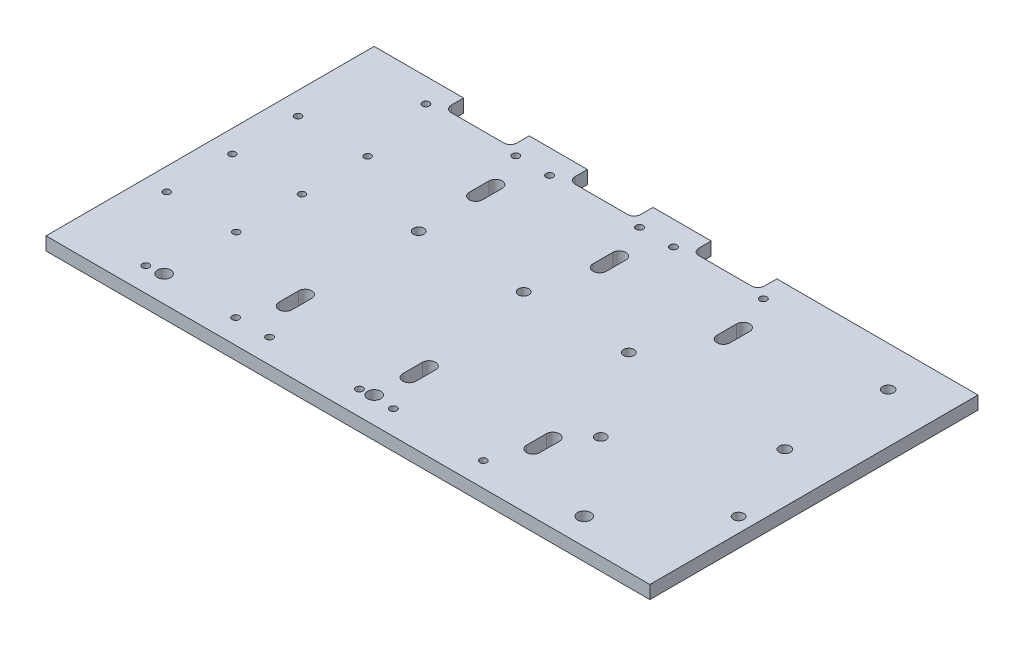
SolidWorks part; units mm, degrees
ref_plane "Front Plane" through (0, 0, 0) normal (0, 0, 1) x (1, 0, 0)
ref_plane "Top Plane" through (0, 0, 0) normal (0, 1, 0) x (1, 0, 0)
ref_plane "Right Plane" through (0, 0, 0) normal (1, 0, 0) x (0, 0, -1)
sketch "Sketch1" plane through (0, 0, 0) normal (0, 1, 0) x (1, 0, 0)
  line L1 (0, 0) -> (292.1, 0)
  line L2 (0, 0) -> (0, 158.75)
  line L3 (0, 158.75) -> (292.1, 158.75)
  line L4 (292.1, 0) -> (292.1, 158.75)
  dimension "D1" = 292.1
  dimension "D2" = 158.75
extrude "Boss-Extrude1" add sketch "Sketch1" along normal blind 6.35
sketch "Sketch2" plane through (0, 6.35, 0) normal (0, 1, 0) x (1, 0, 0)
  line L0 (0, 25.4) -> (292.1, 25.4) construction
  line L1 (0, 12.7) -> (292.1, 12.7) construction
  line L3 (146.05, 25.4) -> (146.05, 158.75) construction
  line L4 (0, 158.75) -> (0, 0)
  line L5 (0, 0) -> (292.1, 0)
  line L6 (292.1, 0) -> (292.1, 158.75)
  line L7 (292.1, 158.75) -> (0, 158.75)
  line L8 (0, 158.75) -> (0, 0) construction
  line L9 (0, 0) -> (292.1, 0) construction
  line L10 (292.1, 0) -> (292.1, 158.75) construction
  line L11 (292.1, 158.75) -> (0, 158.75) construction
  line L12 (292.1, 92.075) -> (0, 92.075) construction
  circle A0 centre (146.05, 12.7) radius 3.175
  circle A1 centre (247.65, 12.7) radius 3.175
  circle A2 centre (44.45, 12.7) radius 3.175
  point P8 (146.05, 92.075)
  dimension "D6" = 6.35
  dimension "D7" = 6.35
  dimension "D8" = 6.35
  dimension "D2" = 25.4
  dimension "D3" = 12.7
  dimension "D4" = 101.6
  dimension "D5" = 101.6
  dimension "D1" = 0
extrude "Cut-Extrude2" cut sketch "Sketch2" against normal blind 6.35
ref_plane "Plane2" through (0, 0, -79.375) normal (0, 0, 1) x (1, 0, 0)
ref_plane "Plane3" through (146.05, 0, 0) normal (-1, 0, 0) x (0, 0, 1)
ref_plane "Plane4" through (0, 0, -92.075) normal (0, 0, -1) x (-1, 0, 0)
sketch "Sketch4" plane through (0, 6.35, 0) normal (0, 1, 0) x (1, 0, 0)
  line L0 (92.964, 94.615) -> (83.439, 94.615) construction
  line L1 (83.439, 89.535) -> (92.964, 89.535) construction
  line L2 (143.764, 94.615) -> (134.239, 94.615) construction
  line L3 (134.239, 89.535) -> (143.764, 89.535) construction
  line L4 (194.564, 94.615) -> (185.039, 94.615) construction
  line L5 (185.039, 89.535) -> (194.564, 89.535) construction
  line L6 (270.764, 94.133) -> (270.764, 84.467) construction
  line L7 (265.43, 84.467) -> (265.43, 94.133) construction
  line L8 (265.43, 134.467) -> (265.43, 144.133) construction
  line L9 (270.764, 144.133) -> (270.764, 134.467) construction
  line L10 (211.4042, 52.4764) -> (218.4146, 52.4764)
  line L11 (211.4042, 74.4728) -> (211.4042, 52.4764)
  line L12 (292.1, 74.4728) -> (211.4042, 74.4728)
  line L13 (292.1, 52.4764) -> (292.1, 74.4728)
  line L14 (285.0896, 52.4764) -> (292.1, 52.4764)
  line L15 (292.1, 47.3964) -> (285.0896, 47.3964)
  line L16 (292.1, 25.4) -> (292.1, 47.3964)
  line L17 (211.4042, 25.4) -> (292.1, 25.4)
  line L18 (211.4042, 47.3964) -> (211.4042, 25.4)
  line L19 (218.4146, 47.3964) -> (211.4042, 47.3964)
  line L20 (211.4042, 52.4764) -> (218.4146, 52.4764) construction
  line L21 (211.4042, 74.4728) -> (211.4042, 52.4764) construction
  line L22 (292.1, 74.4728) -> (211.4042, 74.4728) construction
  line L23 (292.1, 52.4764) -> (292.1, 74.4728) construction
  line L24 (285.0896, 52.4764) -> (292.1, 52.4764) construction
  line L25 (292.1, 47.3964) -> (285.0896, 47.3964) construction
  line L26 (292.1, 25.4) -> (292.1, 47.3964) construction
  line L27 (211.4042, 25.4) -> (292.1, 25.4) construction
  line L28 (211.4042, 47.3964) -> (211.4042, 25.4) construction
  line L29 (218.4146, 47.3964) -> (211.4042, 47.3964) construction
  line L30 (92.964, 94.615) -> (83.439, 94.615) construction
  line L31 (83.439, 89.535) -> (92.964, 89.535) construction
  line L32 (143.764, 94.615) -> (134.239, 94.615) construction
  line L33 (134.239, 89.535) -> (143.764, 89.535) construction
  line L34 (194.564, 94.615) -> (185.039, 94.615) construction
  line L35 (185.039, 89.535) -> (194.564, 89.535) construction
  line L36 (270.764, 94.133) -> (270.764, 84.467) construction
  line L37 (265.43, 84.467) -> (265.43, 94.133) construction
  line L38 (265.43, 134.467) -> (265.43, 144.133) construction
  line L39 (270.764, 144.133) -> (270.764, 134.467) construction
  line L40 (194.564, 92.075) -> (185.039, 92.075) construction
  line L41 (185.039, 92.075) -> (143.764, 92.075) construction
  line L42 (143.764, 92.075) -> (134.239, 92.075) construction
  line L43 (134.239, 92.075) -> (92.964, 92.075) construction
  line L44 (92.964, 92.075) -> (83.439, 92.075) construction
  line L45 (268.097, 84.467) -> (268.097, 94.133) construction
  line L46 (268.097, 94.133) -> (268.097, 134.467) construction
  line L47 (268.097, 134.467) -> (268.097, 144.133) construction
  line L48 (153.9042, 9.125) -> (153.9042, 149.625) construction
  line L49 (153.9042, 149.625) -> (203.9042, 149.625) construction
  line L50 (203.9042, 149.625) -> (203.9042, 9.125) construction
  line L51 (203.9042, 9.125) -> (153.9042, 9.125) construction
  line L52 (34.1164, 149.625) -> (34.1164, 9.125)
  line L53 (84.1164, 149.625) -> (34.1164, 149.625)
  line L54 (84.1164, 9.125) -> (84.1164, 149.625)
  line L55 (34.1164, 9.125) -> (84.1164, 9.125)
  line L56 (34.1164, 149.625) -> (34.1164, 9.125) construction
  line L57 (84.1164, 149.625) -> (34.1164, 149.625) construction
  line L58 (84.1164, 9.125) -> (84.1164, 149.625) construction
  line L59 (34.1164, 9.125) -> (84.1164, 9.125) construction
  line L60 (94.0103, 9.125) -> (94.0103, 149.625) construction
  line L61 (94.0103, 149.625) -> (144.0103, 149.625) construction
  line L62 (144.0103, 149.625) -> (144.0103, 9.125) construction
  line L63 (144.0103, 9.125) -> (94.0103, 9.125) construction
  line L64 (153.9042, 9.125) -> (153.9042, 149.625) construction
  line L65 (153.9042, 149.625) -> (203.9042, 149.625) construction
  line L66 (203.9042, 149.625) -> (203.9042, 9.125) construction
  line L67 (203.9042, 9.125) -> (153.9042, 9.125) construction
  line L68 (94.0103, 9.125) -> (94.0103, 149.625) construction
  line L69 (94.0103, 149.625) -> (144.0103, 149.625) construction
  line L70 (144.0103, 149.625) -> (144.0103, 9.125) construction
  line L71 (144.0103, 9.125) -> (94.0103, 9.125) construction
  line L72 (147.1853, 130.175) -> (147.1853, 120.65) construction
  line L73 (150.3603, 130.175) -> (150.3603, 120.65)
  line L74 (144.0103, 130.175) -> (144.0103, 120.65)
  line L75 (207.0792, 130.175) -> (207.0792, 120.65) construction
  line L76 (210.2542, 130.175) -> (210.2542, 120.65)
  line L77 (203.9042, 130.175) -> (203.9042, 120.65)
  line L78 (87.2914, 130.175) -> (87.2914, 120.65) construction
  line L79 (90.4664, 130.175) -> (90.4664, 120.65)
  line L80 (84.1164, 130.175) -> (84.1164, 120.65)
  line L81 (147.1853, 130.175) -> (87.2914, 130.175) construction
  line L82 (87.2914, 38.1) -> (87.2914, 28.575) construction
  line L83 (90.4664, 38.1) -> (90.4664, 28.575)
  line L84 (84.1164, 38.1) -> (84.1164, 28.575)
  line L85 (207.0792, 38.1) -> (207.0792, 28.575) construction
  line L86 (210.2542, 38.1) -> (210.2542, 28.575)
  line L87 (203.9042, 38.1) -> (203.9042, 28.575)
  line L88 (147.1853, 38.1) -> (147.1853, 28.575) construction
  line L89 (150.3603, 38.1) -> (150.3603, 28.575)
  line L90 (144.0103, 38.1) -> (144.0103, 28.575)
  line L91 (147.1853, 28.575) -> (207.0792, 28.575) construction
  line L92 (207.0792, 28.575) -> (63.9767, 28.575) construction
  line L93 (147.1853, 120.65) -> (147.1853, 38.1) construction
  line L94 (207.0792, 120.65) -> (207.0792, 38.1) construction
  line L95 (87.2914, 120.65) -> (87.2914, 74.3204) construction
  line L96 (292.1, 25.4) -> (0, 25.4) construction
  line L97 (292.1, 25.4) -> (0, 25.4) construction
  line L98 (191.6042, 152.8) -> (166.2042, 152.8) construction
  line L99 (191.6042, 149.625) -> (166.2042, 149.625)
  line L100 (76.2, 117.475) -> (215.9, 117.475) construction
  line L101 (131.7103, 152.8) -> (106.3103, 152.8) construction
  line L102 (131.7103, 149.625) -> (106.3103, 149.625)
  line L103 (76.2, 117.475) -> (215.9, 117.475) construction
  line L104 (71.8164, 152.8) -> (46.4164, 152.8) construction
  line L105 (71.8164, 149.625) -> (46.4164, 149.625)
  line L107 (178.9042, 9.125) -> (178.9042, 158.75) construction
  line L108 (119.0103, 9.125) -> (119.0103, 158.75) construction
  line L109 (59.1164, 9.125) -> (59.1164, 158.75) construction
  line L110 (166.2042, 152.8) -> (131.7103, 152.8) construction
  line L111 (106.3103, 152.8) -> (71.8164, 152.8) construction
  line L112 (163.0292, 152.8) -> (163.0292, 158.75)
  line L113 (194.7792, 152.8) -> (194.7792, 158.75)
  line L114 (134.8853, 152.8) -> (134.8853, 158.75)
  line L115 (103.1353, 152.8) -> (103.1353, 158.75)
  line L116 (147.1853, 74.3204) -> (207.0792, 74.3204) construction
  line L117 (207.0792, 74.3204) -> (87.2914, 74.3204) construction
  line L118 (0, 133.35) -> (292.1, 133.35) construction
  line L119 (0, 158.75) -> (0, 0) construction
  line L120 (292.1, 0) -> (292.1, 158.75) construction
  line L121 (292.1, 158.75) -> (0, 158.75) construction
  line L122 (43.2414, 152.8) -> (43.2414, 158.75)
  line L123 (74.9914, 152.8) -> (74.9914, 158.75)
  line L124 (74.9914, 158.75) -> (43.2414, 158.75)
  line L125 (134.8853, 158.75) -> (103.1353, 158.75)
  line L126 (194.7792, 158.75) -> (163.0292, 158.75)
  line L144 (87.2914, 74.3204) -> (87.2914, 9.0265) construction
  circle A0 centre (88.2015, 92.075) radius 2.54
  arc A1 (92.964, 89.535) -> (92.964, 94.615) centre (92.964, 92.075) ccw construction
  arc A2 (83.439, 94.615) -> (83.439, 89.535) centre (83.439, 92.075) ccw construction
  arc A3 (285.0896, 52.4764) -> (285.0896, 47.3964) centre (285.0896, 49.9364) ccw
  arc A4 (218.4146, 47.3964) -> (218.4146, 52.4764) centre (218.4146, 49.9364) ccw
  arc A5 (285.0896, 52.4764) -> (285.0896, 47.3964) centre (285.0896, 49.9364) ccw construction
  arc A6 (218.4146, 47.3964) -> (218.4146, 52.4764) centre (218.4146, 49.9364) ccw construction
  arc A7 (134.239, 94.615) -> (134.239, 89.535) centre (134.239, 92.075) ccw construction
  arc A8 (143.764, 89.535) -> (143.764, 94.615) centre (143.764, 92.075) ccw construction
  arc A9 (185.039, 94.615) -> (185.039, 89.535) centre (185.039, 92.075) ccw construction
  arc A10 (194.564, 89.535) -> (194.564, 94.615) centre (194.564, 92.075) ccw construction
  arc A11 (265.43, 84.467) -> (270.764, 84.467) centre (268.097, 84.467) ccw construction
  arc A12 (270.764, 94.133) -> (265.43, 94.133) centre (268.097, 94.133) ccw construction
  arc A13 (265.43, 134.467) -> (270.764, 134.467) centre (268.097, 134.467) ccw construction
  arc A14 (270.764, 144.133) -> (265.43, 144.133) centre (268.097, 144.133) ccw construction
  arc A15 (92.964, 89.535) -> (92.964, 94.615) centre (92.964, 92.075) ccw construction
  arc A16 (83.439, 94.615) -> (83.439, 89.535) centre (83.439, 92.075) ccw construction
  arc A17 (134.239, 94.615) -> (134.239, 89.535) centre (134.239, 92.075) ccw construction
  arc A18 (143.764, 89.535) -> (143.764, 94.615) centre (143.764, 92.075) ccw construction
  arc A19 (185.039, 94.615) -> (185.039, 89.535) centre (185.039, 92.075) ccw construction
  arc A20 (194.564, 89.535) -> (194.564, 94.615) centre (194.564, 92.075) ccw construction
  arc A21 (265.43, 84.467) -> (270.764, 84.467) centre (268.097, 84.467) ccw construction
  arc A22 (270.764, 94.133) -> (265.43, 94.133) centre (268.097, 94.133) ccw construction
  arc A23 (265.43, 134.467) -> (270.764, 134.467) centre (268.097, 134.467) ccw construction
  arc A24 (270.764, 144.133) -> (265.43, 144.133) centre (268.097, 144.133) ccw construction
  circle A25 centre (44.45, 111.125) radius 1.651 construction
  circle A26 centre (44.45, 79.375) radius 1.651 construction
  circle A27 centre (44.45, 47.625) radius 1.651 construction
  circle A28 centre (10.795, 111.125) radius 1.651 construction
  circle A29 centre (10.795, 79.375) radius 1.651 construction
  circle A30 centre (10.795, 47.625) radius 1.651 construction
  circle A31 centre (44.45, 111.125) radius 1.651
  circle A32 centre (44.45, 79.375) radius 1.651
  circle A33 centre (44.45, 47.625) radius 1.651
  circle A34 centre (10.795, 111.125) radius 1.651
  circle A35 centre (10.795, 79.375) radius 1.651
  circle A36 centre (10.795, 47.625) radius 1.651
  circle A37 centre (139.0015, 92.075) radius 2.54
  circle A38 centre (189.8015, 92.075) radius 2.54
  circle A39 centre (218.4146, 49.9364) radius 2.54
  circle A40 centre (285.0896, 49.9364) radius 2.54
  circle A41 centre (268.097, 139.3) radius 2.667
  circle A42 centre (268.097, 89.3) radius 2.667
  arc A43 (150.3603, 130.175) -> (144.0103, 130.175) centre (147.1853, 130.175) ccw
  arc A44 (144.0103, 120.65) -> (150.3603, 120.65) centre (147.1853, 120.65) ccw
  arc A45 (210.2542, 130.175) -> (203.9042, 130.175) centre (207.0792, 130.175) ccw
  arc A46 (203.9042, 120.65) -> (210.2542, 120.65) centre (207.0792, 120.65) ccw
  arc A47 (90.4664, 130.175) -> (84.1164, 130.175) centre (87.2914, 130.175) ccw
  arc A48 (84.1164, 120.65) -> (90.4664, 120.65) centre (87.2914, 120.65) ccw
  arc A49 (90.4664, 38.1) -> (84.1164, 38.1) centre (87.2914, 38.1) ccw
  arc A50 (84.1164, 28.575) -> (90.4664, 28.575) centre (87.2914, 28.575) ccw
  arc A51 (210.2542, 38.1) -> (203.9042, 38.1) centre (207.0792, 38.1) ccw
  arc A52 (203.9042, 28.575) -> (210.2542, 28.575) centre (207.0792, 28.575) ccw
  arc A53 (150.3603, 38.1) -> (144.0103, 38.1) centre (147.1853, 38.1) ccw
  arc A54 (144.0103, 28.575) -> (150.3603, 28.575) centre (147.1853, 28.575) ccw
  arc A55 (191.6042, 149.625) -> (194.7792, 152.8) centre (191.6042, 152.8) ccw
  arc A56 (163.0292, 152.8) -> (166.2042, 149.625) centre (166.2042, 152.8) ccw
  arc A57 (131.7103, 149.625) -> (134.8853, 152.8) centre (131.7103, 152.8) ccw
  arc A58 (103.1353, 152.8) -> (106.3103, 149.625) centre (106.3103, 152.8) ccw
  arc A59 (71.8164, 149.625) -> (74.9914, 152.8) centre (71.8164, 152.8) ccw
  arc A60 (43.2414, 152.8) -> (46.4164, 149.625) centre (46.4164, 152.8) ccw
  spline S0 degree 3 poles (96.5103, 145.425) (99.9103, 145.425) (99.9103, 148.825) (96.5103, 148.825) (93.1103, 148.825) (93.1103, 145.425) (96.5103, 145.425) (99.9103, 145.425) (99.9103, 148.825) knots -0.5 0 0 0 0.5 0.5 0.5 1 1 1 1.5 1.5 1.5 weights 1 0.333333 0.333333 1 0.333333 0.333333 1 0.333333 0.333333 only from (96.5103, 145.425) to (96.5103, 145.425) construction
  spline S1 degree 3 poles (80.1164, 145.425) (83.5164, 145.425) (83.5164, 148.825) (80.1164, 148.825) (76.7164, 148.825) (76.7164, 145.425) (80.1164, 145.425) (83.5164, 145.425) (83.5164, 148.825) knots -0.5 0 0 0 0.5 0.5 0.5 1 1 1 1.5 1.5 1.5 weights 1 0.333333 0.333333 1 0.333333 0.333333 1 0.333333 0.333333 only from (80.1164, 145.425) to (80.1164, 145.425) construction
  spline S2 degree 3 poles (36.6164, 145.425) (40.0164, 145.425) (40.0164, 148.825) (36.6164, 148.825) (33.2164, 148.825) (33.2164, 145.425) (36.6164, 145.425) (40.0164, 145.425) (40.0164, 148.825) knots -0.5 0 0 0 0.5 0.5 0.5 1 1 1 1.5 1.5 1.5 weights 1 0.333333 0.333333 1 0.333333 0.333333 1 0.333333 0.333333 only from (36.6164, 145.425) to (36.6164, 145.425) construction
  spline S3 degree 3 poles (140.0103, 145.425) (143.4103, 145.425) (143.4103, 148.825) (140.0103, 148.825) (136.6103, 148.825) (136.6103, 145.425) (140.0103, 145.425) (143.4103, 145.425) (143.4103, 148.825) knots -0.5 0 0 0 0.5 0.5 0.5 1 1 1 1.5 1.5 1.5 weights 1 0.333333 0.333333 1 0.333333 0.333333 1 0.333333 0.333333 only from (140.0103, 145.425) to (140.0103, 145.425) construction
  spline S4 degree 3 poles (156.4042, 145.425) (159.8042, 145.425) (159.8042, 148.825) (156.4042, 148.825) (153.0042, 148.825) (153.0042, 145.425) (156.4042, 145.425) (159.8042, 145.425) (159.8042, 148.825) knots -0.5 0 0 0 0.5 0.5 0.5 1 1 1 1.5 1.5 1.5 weights 1 0.333333 0.333333 1 0.333333 0.333333 1 0.333333 0.333333 only from (156.4042, 145.425) to (156.4042, 145.425) construction
  spline S5 degree 3 poles (199.9042, 145.425) (203.3042, 145.425) (203.3042, 148.825) (199.9042, 148.825) (196.5042, 148.825) (196.5042, 145.425) (199.9042, 145.425) (203.3042, 145.425) (203.3042, 148.825) knots -0.5 0 0 0 0.5 0.5 0.5 1 1 1 1.5 1.5 1.5 weights 1 0.333333 0.333333 1 0.333333 0.333333 1 0.333333 0.333333 only from (199.9042, 145.425) to (199.9042, 145.425) construction
  spline S6 degree 3 poles (140.0103, 9.925) (143.4103, 9.925) (143.4103, 13.325) (140.0103, 13.325) (136.6103, 13.325) (136.6103, 9.925) (140.0103, 9.925) (143.4103, 9.925) (143.4103, 13.325) knots -0.5 0 0 0 0.5 0.5 0.5 1 1 1 1.5 1.5 1.5 weights 1 0.333333 0.333333 1 0.333333 0.333333 1 0.333333 0.333333 only from (140.0103, 9.925) to (140.0103, 9.925) construction
  spline S7 degree 3 poles (96.5103, 9.925) (99.9103, 9.925) (99.9103, 13.325) (96.5103, 13.325) (93.1103, 13.325) (93.1103, 9.925) (96.5103, 9.925) (99.9103, 9.925) (99.9103, 13.325) knots -0.5 0 0 0 0.5 0.5 0.5 1 1 1 1.5 1.5 1.5 weights 1 0.333333 0.333333 1 0.333333 0.333333 1 0.333333 0.333333 only from (96.5103, 9.925) to (96.5103, 9.925) construction
  spline S8 degree 3 poles (80.1164, 9.925) (83.5164, 9.925) (83.5164, 13.325) (80.1164, 13.325) (76.7164, 13.325) (76.7164, 9.925) (80.1164, 9.925) (83.5164, 9.925) (83.5164, 13.325) knots -0.5 0 0 0 0.5 0.5 0.5 1 1 1 1.5 1.5 1.5 weights 1 0.333333 0.333333 1 0.333333 0.333333 1 0.333333 0.333333 only from (80.1164, 9.925) to (80.1164, 9.925) construction
  spline S9 degree 3 poles (36.6164, 9.925) (40.0164, 9.925) (40.0164, 13.325) (36.6164, 13.325) (33.2164, 13.325) (33.2164, 9.925) (36.6164, 9.925) (40.0164, 9.925) (40.0164, 13.325) knots -0.5 0 0 0 0.5 0.5 0.5 1 1 1 1.5 1.5 1.5 weights 1 0.333333 0.333333 1 0.333333 0.333333 1 0.333333 0.333333 only from (36.6164, 9.925) to (36.6164, 9.925) construction
  spline S10 degree 3 poles (156.4042, 9.925) (159.8042, 9.925) (159.8042, 13.325) (156.4042, 13.325) (153.0042, 13.325) (153.0042, 9.925) (156.4042, 9.925) (159.8042, 9.925) (159.8042, 13.325) knots -0.5 0 0 0 0.5 0.5 0.5 1 1 1 1.5 1.5 1.5 weights 1 0.333333 0.333333 1 0.333333 0.333333 1 0.333333 0.333333 only from (156.4042, 9.925) to (156.4042, 9.925) construction
  spline S11 degree 3 poles (199.9042, 9.925) (203.3042, 9.925) (203.3042, 13.325) (199.9042, 13.325) (196.5042, 13.325) (196.5042, 9.925) (199.9042, 9.925) (203.3042, 9.925) (203.3042, 13.325) knots -0.5 0 0 0 0.5 0.5 0.5 1 1 1 1.5 1.5 1.5 weights 1 0.333333 0.333333 1 0.333333 0.333333 1 0.333333 0.333333 only from (199.9042, 9.925) to (199.9042, 9.925) construction
  spline S12 degree 3 poles (96.5103, 145.425) (99.9103, 145.425) (99.9103, 148.825) (96.5103, 148.825) (93.1103, 148.825) (93.1103, 145.425) (96.5103, 145.425) (99.9103, 145.425) (99.9103, 148.825) knots -0.5 0 0 0 0.5 0.5 0.5 1 1 1 1.5 1.5 1.5 weights 1 0.333333 0.333333 1 0.333333 0.333333 1 0.333333 0.333333 only from (96.5103, 145.425) to (96.5103, 145.425)
  spline S13 degree 3 poles (80.1164, 145.425) (83.5164, 145.425) (83.5164, 148.825) (80.1164, 148.825) (76.7164, 148.825) (76.7164, 145.425) (80.1164, 145.425) (83.5164, 145.425) (83.5164, 148.825) knots -0.5 0 0 0 0.5 0.5 0.5 1 1 1 1.5 1.5 1.5 weights 1 0.333333 0.333333 1 0.333333 0.333333 1 0.333333 0.333333 only from (80.1164, 145.425) to (80.1164, 145.425)
  spline S14 degree 3 poles (36.6164, 145.425) (40.0164, 145.425) (40.0164, 148.825) (36.6164, 148.825) (33.2164, 148.825) (33.2164, 145.425) (36.6164, 145.425) (40.0164, 145.425) (40.0164, 148.825) knots -0.5 0 0 0 0.5 0.5 0.5 1 1 1 1.5 1.5 1.5 weights 1 0.333333 0.333333 1 0.333333 0.333333 1 0.333333 0.333333 only from (36.6164, 145.425) to (36.6164, 145.425)
  spline S15 degree 3 poles (140.0103, 145.425) (143.4103, 145.425) (143.4103, 148.825) (140.0103, 148.825) (136.6103, 148.825) (136.6103, 145.425) (140.0103, 145.425) (143.4103, 145.425) (143.4103, 148.825) knots -0.5 0 0 0 0.5 0.5 0.5 1 1 1 1.5 1.5 1.5 weights 1 0.333333 0.333333 1 0.333333 0.333333 1 0.333333 0.333333 only from (140.0103, 145.425) to (140.0103, 145.425)
  spline S16 degree 3 poles (156.4042, 145.425) (159.8042, 145.425) (159.8042, 148.825) (156.4042, 148.825) (153.0042, 148.825) (153.0042, 145.425) (156.4042, 145.425) (159.8042, 145.425) (159.8042, 148.825) knots -0.5 0 0 0 0.5 0.5 0.5 1 1 1 1.5 1.5 1.5 weights 1 0.333333 0.333333 1 0.333333 0.333333 1 0.333333 0.333333 only from (156.4042, 145.425) to (156.4042, 145.425)
  spline S17 degree 3 poles (199.9042, 145.425) (203.3042, 145.425) (203.3042, 148.825) (199.9042, 148.825) (196.5042, 148.825) (196.5042, 145.425) (199.9042, 145.425) (203.3042, 145.425) (203.3042, 148.825) knots -0.5 0 0 0 0.5 0.5 0.5 1 1 1 1.5 1.5 1.5 weights 1 0.333333 0.333333 1 0.333333 0.333333 1 0.333333 0.333333 only from (199.9042, 145.425) to (199.9042, 145.425)
  spline S18 degree 3 poles (140.0103, 9.925) (143.4103, 9.925) (143.4103, 13.325) (140.0103, 13.325) (136.6103, 13.325) (136.6103, 9.925) (140.0103, 9.925) (143.4103, 9.925) (143.4103, 13.325) knots -0.5 0 0 0 0.5 0.5 0.5 1 1 1 1.5 1.5 1.5 weights 1 0.333333 0.333333 1 0.333333 0.333333 1 0.333333 0.333333 only from (140.0103, 9.925) to (140.0103, 9.925)
  spline S19 degree 3 poles (96.5103, 9.925) (99.9103, 9.925) (99.9103, 13.325) (96.5103, 13.325) (93.1103, 13.325) (93.1103, 9.925) (96.5103, 9.925) (99.9103, 9.925) (99.9103, 13.325) knots -0.5 0 0 0 0.5 0.5 0.5 1 1 1 1.5 1.5 1.5 weights 1 0.333333 0.333333 1 0.333333 0.333333 1 0.333333 0.333333 only from (96.5103, 9.925) to (96.5103, 9.925)
  spline S20 degree 3 poles (80.1164, 9.925) (83.5164, 9.925) (83.5164, 13.325) (80.1164, 13.325) (76.7164, 13.325) (76.7164, 9.925) (80.1164, 9.925) (83.5164, 9.925) (83.5164, 13.325) knots -0.5 0 0 0 0.5 0.5 0.5 1 1 1 1.5 1.5 1.5 weights 1 0.333333 0.333333 1 0.333333 0.333333 1 0.333333 0.333333 only from (80.1164, 9.925) to (80.1164, 9.925)
  spline S21 degree 3 poles (36.6164, 9.925) (40.0164, 9.925) (40.0164, 13.325) (36.6164, 13.325) (33.2164, 13.325) (33.2164, 9.925) (36.6164, 9.925) (40.0164, 9.925) (40.0164, 13.325) knots -0.5 0 0 0 0.5 0.5 0.5 1 1 1 1.5 1.5 1.5 weights 1 0.333333 0.333333 1 0.333333 0.333333 1 0.333333 0.333333 only from (36.6164, 9.925) to (36.6164, 9.925)
  spline S22 degree 3 poles (156.4042, 9.925) (159.8042, 9.925) (159.8042, 13.325) (156.4042, 13.325) (153.0042, 13.325) (153.0042, 9.925) (156.4042, 9.925) (159.8042, 9.925) (159.8042, 13.325) knots -0.5 0 0 0 0.5 0.5 0.5 1 1 1 1.5 1.5 1.5 weights 1 0.333333 0.333333 1 0.333333 0.333333 1 0.333333 0.333333 only from (156.4042, 9.925) to (156.4042, 9.925)
  spline S23 degree 3 poles (199.9042, 9.925) (203.3042, 9.925) (203.3042, 13.325) (199.9042, 13.325) (196.5042, 13.325) (196.5042, 9.925) (199.9042, 9.925) (203.3042, 9.925) (203.3042, 13.325) knots -0.5 0 0 0 0.5 0.5 0.5 1 1 1 1.5 1.5 1.5 weights 1 0.333333 0.333333 1 0.333333 0.333333 1 0.333333 0.333333 only from (199.9042, 9.925) to (199.9042, 9.925)
  point P100 (147.1853, 125.4125)
  point P105 (207.0792, 125.4125)
  point P112 (87.2914, 125.4125)
  point P121 (87.2914, 33.3375)
  point P128 (207.0792, 33.3375)
  point P135 (147.1853, 33.3375)
  point P142 (147.1853, 25.4)
  point P152 (178.9042, 152.8)
  point P155 (0, 0)
  point P159 (0, 0)
  point P160 (119.0103, 152.8)
  point P165 (0, 0)
  point P166 (0, 0)
  point P167 (59.1164, 152.8)
  point P175 (0, 0)
  point P180 (0, 0)
  point P181 (87.2914, 123.1729)
  dimension "D3" = 3.175
  dimension "D5" = 3.175
  dimension "D4" = 25.4
  dimension "D7" = 25.4
  dimension "D1" = 0
  dimension "D2" = 0
extrude "Cut-Extrude5" cut sketch "Sketch4" against normal through all
equation "\"D5@Sketch2\"=\"D4@Sketch2\""
equation "\"D7@Sketch2\"=\"D6@Sketch2\""
equation "\"D8@Sketch2\"=\"D7@Sketch2\""
